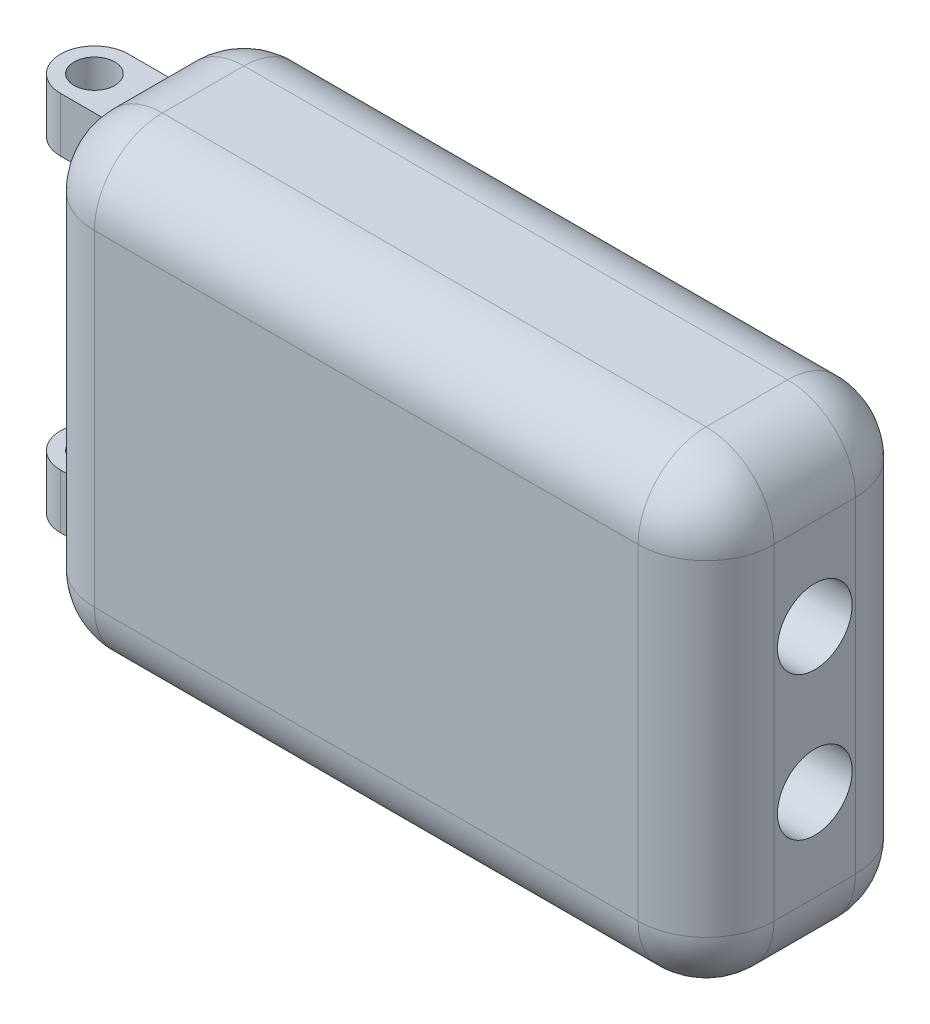
SolidWorks part; units mm, degrees
ref_plane "Plan de face" through (0, 0, 0) normal (0, 0, 1) x (1, 0, 0)
ref_plane "Plan de dessus" through (0, 0, 0) normal (0, 1, 0) x (1, 0, 0)
ref_plane "Plan de droite" through (0, 0, 0) normal (1, 0, 0) x (0, 0, -1)
sketch "Esquisse1" plane through (0, 0, 0) normal (0, 0, 1) x (1, 0, 0)
  line L1 (0, 0) -> (50, 0)
  line L2 (0, 0) -> (0, 34)
  line L3 (0, 34) -> (50, 34)
  line L4 (50, 0) -> (50, 34)
  dimension "D1" = 34
  dimension "D2" = 50
extrude "Boss.-Extru.1" add sketch "Esquisse1" along normal blind 30
sketch "Esquisse10" plane through (0, 34, 0) normal (0, 1, 0) x (1, 0, 0)
  line L0 (0, 0) -> (0, -12.5) construction
  line L1 (0, -30) -> (0, 0) construction
  line L2 (0, -12.5) -> (0, -17.5)
  line L3 (0, -17.5) -> (0, -30) construction
  line L4 (0, -12.5) -> (-3, -12.5)
  line L5 (-3, -12.5) -> (-3, -17.5) construction
  line L6 (-3, -17.5) -> (0, -17.5)
  arc A1 (-3, -12.5) -> (-3, -17.5) centre (-3, -15) ccw
  circle A2 centre (-3, -15) radius 1.5
  dimension "D3" = 3
  dimension "D1" = 5
  dimension "D2" = 3
extrude "Boss.-Extru.3" add sketch "Esquisse10" against normal blind 7
ref_plane "Plan2" through (0, 17, 0) normal (0, 1, 0) x (1, 0, 0)
mirror "Symétrie2" about plane through (0, 17, 0) normal (0, 1, 0) of "Boss.-Extru.3"
sketch "Esquisse11" plane through (0, 0, 0) normal (-1, 0, 0) x (0, 0, 1)
  line L2 (17.5, 27) -> (12.5, 7) construction
  line L3 (15, 22.275) -> (15, 11.725) construction
  line L4 (30, 34) -> (17.5, 34) construction
  line L5 (10.3812, 11.725) -> (12.6906, 7.725)
  line L6 (12.6906, 7.725) -> (17.3094, 7.725)
  line L7 (17.3094, 7.725) -> (19.6188, 11.725)
  line L8 (19.6188, 11.725) -> (17.3094, 15.725)
  line L9 (17.3094, 15.725) -> (12.6906, 15.725)
  line L10 (12.6906, 15.725) -> (10.3812, 11.725)
  line L11 (10.3812, 22.275) -> (12.6906, 18.275)
  line L12 (12.6906, 18.275) -> (17.3094, 18.275)
  line L13 (17.3094, 18.275) -> (19.6188, 22.275)
  line L14 (19.6188, 22.275) -> (17.3094, 26.275)
  line L15 (17.3094, 26.275) -> (12.6906, 26.275)
  line L16 (12.6906, 26.275) -> (10.3812, 22.275)
  circle A0 centre (15, 11.725) radius 4 construction
  circle A1 centre (15, 22.275) radius 4 construction
  point P9 (15, 17)
  dimension "D3" = 4.725
  dimension "D4" = 8
extrude "Enlèv. mat.-Extru.6" cut sketch "Esquisse11" against normal blind 45
sketch "Esquisse12" plane through (0, 0, 0) normal (-1, 0, 0) x (0, 0, 1)
  line L0 (12.6906, 7.725) -> (17.3094, 15.725) construction
  line L1 (12.6906, 18.275) -> (17.3094, 26.275) construction
  circle A0 centre (15, 11.725) radius 2.75
  circle A1 centre (15, 22.275) radius 2.75
  dimension "D1" = 5.5
extrude "Enlèv. mat.-Extru.7" cut sketch "Esquisse12" against normal through all
sketch "Esquisse13" plane through (0, 0, 0) normal (-1, 0, 0) x (0, 0, 1)
  line L0 (12.5, 34) -> (0, 34) construction
  line L1 (0, 0) -> (7, 0)
  line L2 (0, 0) -> (0, 34)
  line L3 (0, 34) -> (7, 34)
  line L4 (7, 0) -> (7, 34)
  line L5 (30, 34) -> (17.5, 34) construction
  line L6 (30, 0) -> (23, 0)
  line L7 (30, 0) -> (30, 34)
  line L8 (30, 34) -> (23, 34)
  line L9 (23, 0) -> (23, 34)
  dimension "D1" = 7
extrude "Enlèv. mat.-Extru.8" cut sketch "Esquisse13" against normal through all
sketch "Esquisse14" plane through (50, 0, 0) normal (1, 0, 0) x (0, 0, -1)
  circle A0 centre (-15, 22.275) radius 6
  circle A1 centre (-15, 11.725) radius 6
  dimension "D1" = 12
sketch "Esquisse15" plane through (0, 34, 0) normal (0, 1, 0) x (1, 0, 0)
  line L1 (0, -12.5) -> (-7.1323, -12.5)
  line L2 (0, -12.5) -> (0, -18.0749)
  line L3 (0, -18.0749) -> (-7.1323, -18.0749)
  line L4 (-7.1323, -12.5) -> (-7.1323, -18.0749)
extrude "Enlèv. mat.-Extru.9" cut sketch "Esquisse15" against normal blind 3
sketch "Esquisse16" plane through (0, 0, 0) normal (0, -1, 0) x (1, 0, 0)
  line L0 (0, 12.5) -> (0, 7) construction
  line L1 (0, 16.7321) -> (-3, 18.4641) construction
  line L2 (-3, 18.4641) -> (-6, 16.7321)
  line L3 (-6, 16.7321) -> (-6, 13.2679)
  line L4 (-6, 13.2679) -> (-3, 11.5359)
  line L5 (-3, 11.5359) -> (0, 13.2679) construction
  line L6 (0, 13.2679) -> (0, 16.7321)
  line L7 (0, 13.2679) -> (0, 11.5359)
  line L8 (0, 11.5359) -> (-3, 11.5359)
  line L9 (0, 16.7321) -> (0, 18.4641)
  line L10 (0, 23) -> (0, 17.5) construction
  line L11 (0, 18.4641) -> (-3, 18.4641)
  circle A0 centre (-3, 15) radius 3 construction
  dimension "D1" = 6
extrude "Enlèv. mat.-Extru.10" cut sketch "Esquisse16" against normal blind 3
fillet "Congé1" radius 5 12 edges at (25, 34, 23) (25, 34, 7) (25, 0, 7) (25, 0, 23) (0, 17, 23) (0, 34, 15) (0, 17, 7) (0, 0, 15) (50, 0, 15) (50, 17, 7) (50, 34, 15) (50, 17, 23)
